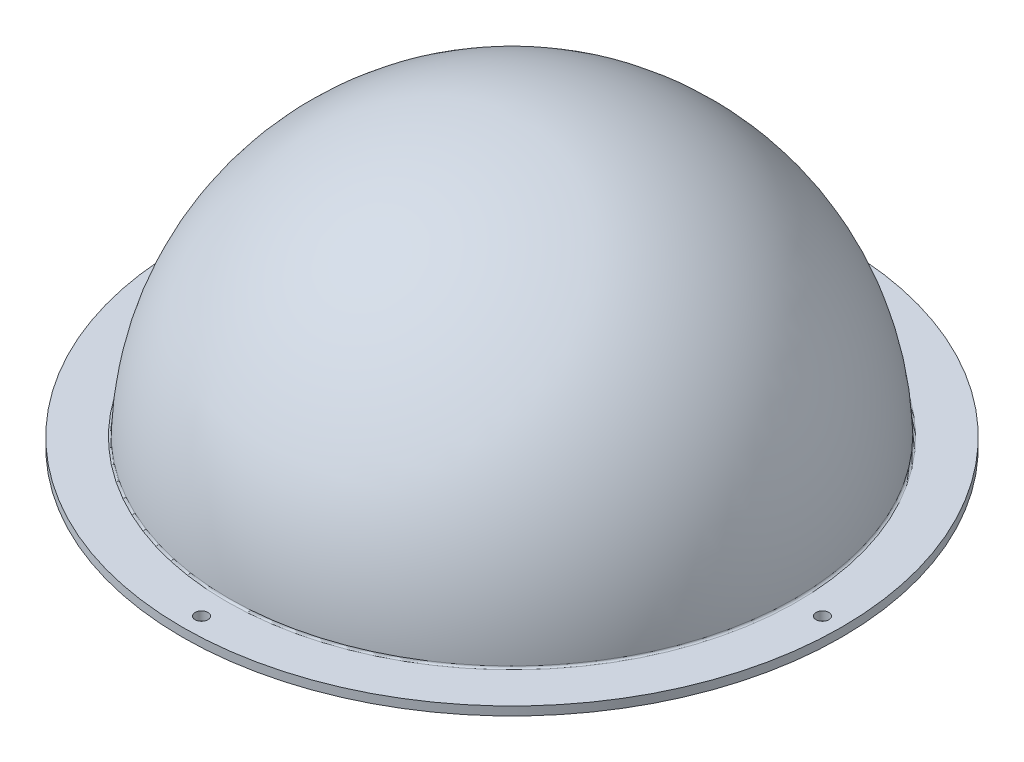
SolidWorks part; units mm, degrees
material "Acrylic (Medium-high impact)"
ref_plane "Front Plane" through (0, 0, 0) normal (0, 0, 1) x (1, 0, 0)
ref_plane "Top Plane" through (0, 0, 0) normal (0, 1, 0) x (1, 0, 0)
ref_plane "Right Plane" through (0, 0, 0) normal (1, 0, 0) x (0, 0, -1)
sketch "Sketch1" plane through (0, 0, 0) normal (0, 0, 1) x (1, 0, 0)
  line L0 (0, 0) -> (0, 73.025)
  line L1 (0, 0) -> (84.9312, 0)
  line L2 (84.9312, 0) -> (84.9312, 2.2352)
  line L3 (84.9312, 2.2352) -> (73.025, 2.2352)
  arc A0 (0, 73.025) -> (73.025, 2.2352) centre (0, -0.0353) cw
  dimension "D1" = 73.025
  dimension "D2" = 11.9062
  dimension "D3" = 2.2352
  dimension "D4" = 73.025
revolve "Revolve1" add sketch "Sketch1" angle 360 about L0
shell "Shell1" thickness 2.2352 removed face at (0, 0, -84.9312)
sketch "Sketch2" plane through (0, 2.2352, 0) normal (0, 1, 0) x (1, 0, 0)
  line L0 (0, 0) -> (0, 84.9312) construction
  circle A1 centre (0, 0) radius 84.9312 construction
  circle A2 centre (0, 0) radius 81.6292
  circle A3 centre (0, 0) radius 81.6292 construction
  circle A4 centre (0, 79.9782) radius 1.651
  circle A5 centre (0, 0) radius 79.9782 construction
  circle A6 centre (79.9782, 0) radius 1.651
  circle A7 centre (0, -79.9782) radius 1.651
  circle A8 centre (-79.9782, 0) radius 1.651
  point P19 (0, 0)
  dimension "D2" = 3.302
  dimension "D1" = 3.302
  dimension "D3" = 4
extrude "Dome Holes" cut sketch "Sketch2" against normal up to surface (2.2352 mm away) up to face at (0, 0, 70.8251)
fillet "Fillet1" radius 2.0955 1 edges at (0, 0, 70.8251)
fillet "Fillet2" radius 0.508 1 edges at (0, 2.2352, -73.025)
